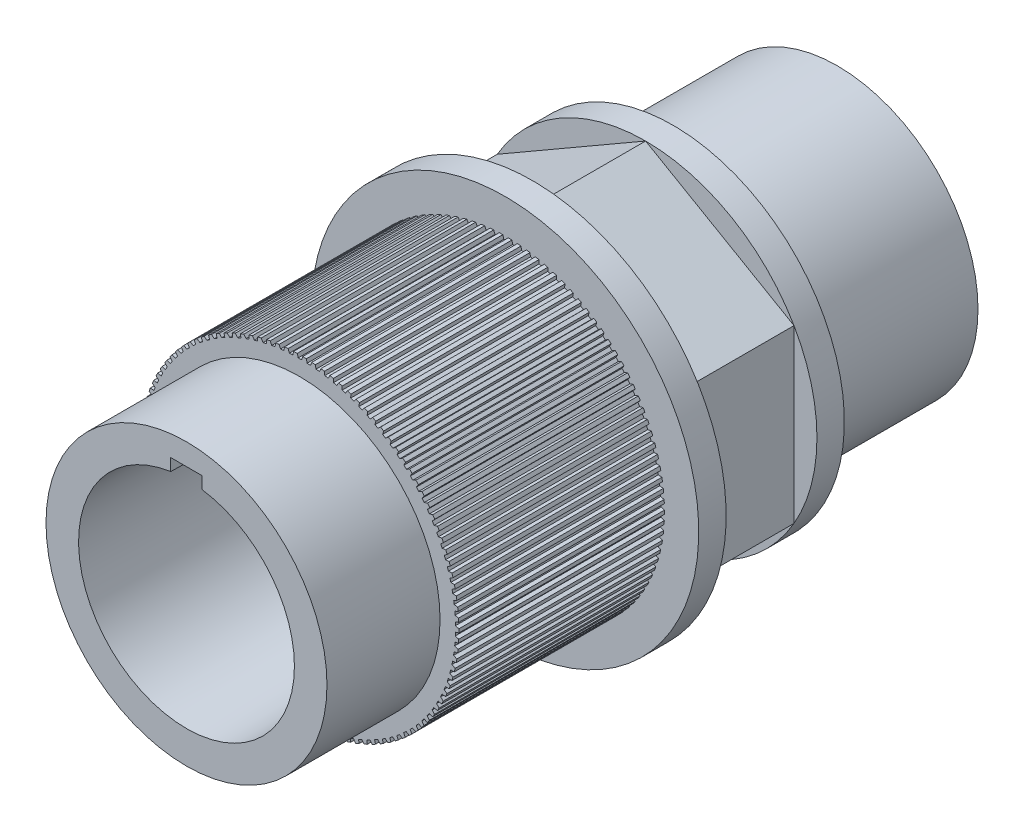
SolidWorks part; units mm, degrees
material "AISI 1010 Steel, hot rolled bar"
ref_plane "Plane1" through (0, 0, 0) normal (0, 0, 1) x (1, 0, 0)
ref_plane "Plane2" through (0, 0, 0) normal (0, 1, 0) x (1, 0, 0)
ref_plane "Plane3" through (0, 0, 0) normal (1, 0, 0) x (0, 0, -1)
sketch "Sketch2" plane through (0, 0, 0) normal (0, 1, 0) x (-1, 0, 0)
  line L0 (0, 0) -> (0, 37.592) construction
  line L1 (0, 37.592) -> (10.414, 37.592)
  line L2 (10.414, 37.592) -> (10.414, 29.21)
  line L3 (10.414, 29.21) -> (11.811, 29.21)
  line L4 (11.811, 29.21) -> (11.811, 13.97)
  line L5 (11.811, 13.97) -> (14.351, 13.97)
  line L6 (14.351, 13.97) -> (14.351, 11.938)
  line L7 (14.351, 11.938) -> (10.414, 11.938)
  line L8 (10.414, 11.938) -> (10.414, 3.556)
  line L9 (10.414, 3.556) -> (12.7, 3.556)
  line L10 (12.7, 3.556) -> (12.7, 1.524)
  line L11 (12.7, 1.524) -> (10.414, 1.524)
  line L12 (10.414, 1.524) -> (10.414, -10.668)
  line L13 (10.414, -10.668) -> (0, -10.668)
  line L14 (0, -27.1943) -> (0, 0) construction
  line L15 (0, 37.592) -> (0, -10.668)
  dimension "D1" = 28.702
  dimension "D2" = 25.4
  dimension "D3" = 20.828
  dimension "D4" = 23.622
  dimension "D5" = 48.26
  dimension "D6" = 8.382
  dimension "D7" = 15.24
  dimension "D8" = 2.032
  dimension "D9" = 8.382
  dimension "D10" = 1.524
revolve "Base-Revolve" add sketch "Sketch2" angle 360 about L0
sketch "Sketch4" plane through (0, 0, 3.556) normal (0, 0, 1) x (1, 0, 0)
  line L0 (0, -12.7) -> (-10.9985, -6.35)
  line L1 (-10.9985, -6.35) -> (-10.9985, 6.35)
  line L2 (-10.9985, 6.35) -> (0, 12.7)
  line L3 (0, 12.7) -> (10.9985, 6.35)
  line L4 (10.9985, 6.35) -> (10.9985, -6.35)
  line L5 (10.9985, -6.35) -> (0, -12.7)
  circle A0 centre (0, 0) radius 12.7 construction
extrude "Boss-Extrude1" add sketch "Sketch4" along normal up to surface (8.382 mm away) up to face at (-10.414, 0, 11.938)
sketch "Sketch7" plane through (0, 0, 37.592) normal (0, 0, 1) x (1, 0, 0)
  circle A0 centre (0, 0) radius 8.001
  dimension "D1" = 16.002
extrude "Cut-Extrude2" cut sketch "Sketch7" against normal through all
sketch "Sketch8" plane through (0, 0, 29.21) normal (0, 0, 1) x (1, 0, 0)
  line L0 (0.2032, -11.8093) -> (0.127, -11.5553)
  line L1 (0.127, -11.5553) -> (-0.127, -11.5553)
  line L2 (-0.127, -11.5553) -> (-0.2032, -11.8093)
  line L3 (0, -11.5553) -> (0, 0) construction
  circle A0 centre (0, 0) radius 11.811 construction
  arc A1 (-0.2032, -11.8093) -> (0.2032, -11.8093) centre (0, 0) ccw
  dimension "D1" = 0.254
  dimension "D2" = 0.254
  dimension "D3" = 0.4064
extrude "Cut-Extrude3" cut sketch "Sketch8" against normal up to surface (15.24 mm away) up to face at (-14.351, 0, 13.97)
pattern_circular "CirPattern1" count 110 every 3.27 about axis through (0, 0, -10.668) along (0, 0, 1) of "Cut-Extrude3"
sketch "Sketch9" plane through (0, 0, 37.592) normal (0, 0, 1) x (1, 0, 0)
  line L0 (1.1665, 8.8138) -> (-1.1665, 8.8138)
  line L1 (-1.1665, 8.8138) -> (-1.1665, 7.9155)
  line L2 (1.1665, 8.8138) -> (1.1665, 7.9155)
  line L3 (0, 8.8138) -> (0, 0) construction
  circle A0 centre (0, 0) radius 8.001 construction
  arc A2 (1.1665, 7.9155) -> (-1.1665, 7.9155) centre (0, 0) ccw
  dimension "D1" = 2.3331
  dimension "D2" = 8.8138
extrude "Cut-Extrude4" cut sketch "Sketch9" against normal blind 13.335
draft "Draft1" type of draft neutral plane draft angle 1 faces to draft 1 face at (8.001, 0, -10.668) neutral plane through (0, 0, 37.592) neutral plane normal (0, 0, 1) parameters "D1"=1
